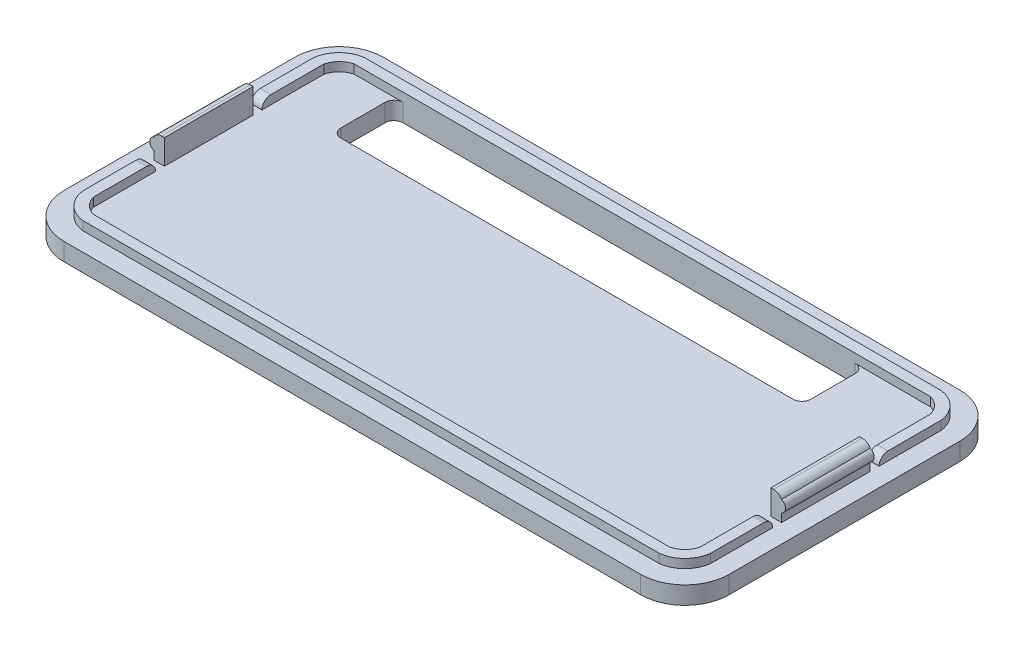
SolidWorks part; units mm, degrees
ref_plane "前视基准面" through (0, 0, 0) normal (0, 0, 1) x (1, 0, 0)
ref_plane "上视基准面" through (0, 0, 0) normal (0, 1, 0) x (1, 0, 0)
ref_plane "右视基准面" through (0, 0, 0) normal (1, 0, 0) x (0, 0, -1)
sketch "zero" plane through (0, 0, 0) normal (0, 1, 0) x (1, 0, 0)
  line L1 (-29.5, 15) -> (29.5, 15)
  line L2 (-32.5, 12) -> (-32.5, -12)
  line L3 (-29.5, -15) -> (29.5, -15)
  line L4 (32.5, 12) -> (32.5, -12)
  line L5 (-32.5, 15) -> (32.5, -15) construction
  line L6 (-32.5, -15) -> (32.5, 15) construction
  line L7 (-25.7, -15) -> (-14.5, -15)
  line L8 (-25.7, -15) -> (-25.7, -9.6569)
  line L9 (-25.7, -9.6569) -> (-14.5, -9.6569)
  line L10 (-14.5, -15) -> (-14.5, -9.6569)
  line L11 (5.2, -15) -> (12.7, -15)
  line L12 (5.2, -15) -> (5.2, -11)
  line L13 (5.2, -11) -> (12.7, -11)
  line L14 (12.7, -15) -> (12.7, -11)
  line L15 (17.8, -15) -> (25.3, -15)
  line L16 (17.8, -15) -> (17.8, -11)
  line L17 (17.8, -11) -> (25.3, -11)
  line L18 (25.3, -15) -> (25.3, -11)
  line L19 (-32.5, 7.7) -> (-19.5, 7.7)
  line L20 (-32.5, 7.7) -> (-32.5, -4.3)
  line L21 (-32.5, -4.3) -> (-19.5, -4.3)
  line L22 (-19.5, 7.7) -> (-19.5, -4.3)
  line L23 (-25.5, 14) -> (25.5, 14)
  line L24 (-25.5, 14) -> (-25.5, 8.8)
  line L25 (-25.5, 8.8) -> (25.5, 8.8)
  line L26 (25.5, 14) -> (25.5, 8.8)
  line L27 (-19.5, 7.2329) -> (-35.5, 7.2329)
  line L28 (-19.5, 7.2329) -> (-19.5, -3.7671)
  line L29 (-19.5, -3.7671) -> (-35.5, -3.7671)
  line L30 (-35.5, 7.2329) -> (-35.5, -3.7671)
  arc A0 (29.5, -15) -> (32.5, -12) centre (29.5, -12) ccw
  arc A1 (29.5, 15) -> (32.5, 12) centre (29.5, 12) cw
  arc A2 (-32.5, -12) -> (-29.5, -15) centre (-29.5, -12) ccw
  arc A3 (-29.5, 15) -> (-32.5, 12) centre (-29.5, 12) ccw
  circle A4 centre (-29, 11.4) radius 3
  circle A5 centre (-29, -11.5) radius 3
  circle A6 centre (29, 11.4) radius 3
  circle A7 centre (29, -11.5) radius 3
  circle A8 centre (-29, 11.4) radius 1.375
  circle A9 centre (-29, -11.5) radius 1.375
  circle A10 centre (29, -11.5) radius 1.375
  circle A11 centre (29, 11.4) radius 1.375
  point P0 (0, 0)
  dimension "D3" = 3
  dimension "D4" = 6
  dimension "D9" = 2.75
  dimension "D1" = 65
  dimension "D2" = 30
  dimension "D5" = 3.6
  dimension "D6" = 3.5
  dimension "D7" = 3.5
  dimension "D8" = 3.5
  dimension "D10" = 12
  dimension "D11" = 7.3
  dimension "D12" = 13
  dimension "D13" = 11.2
  dimension "D14" = 6.8
  dimension "D15" = 19.7
  dimension "D16" = 7.5
  dimension "D17" = 7.5
  dimension "D18" = 5.1
  dimension "D19" = 4
  dimension "D20" = 5.2
  dimension "D21" = 7
  dimension "D22" = 7
  dimension "D23" = 1
  dimension "D24" = 11
  dimension "D25" = 16
sketch "sugar" plane through (0, 0, 0) normal (0, 1, 0) x (1, 0, 0)
  line L1 (-29.5, 15) -> (29.5, 15)
  line L2 (-32.5, 12) -> (-32.5, -12)
  line L3 (-29.5, -15) -> (29.5, -15)
  line L4 (32.5, 12) -> (32.5, -12)
  line L5 (-32.5, 15) -> (32.5, -15) construction
  line L6 (-32.5, -15) -> (32.5, 15) construction
  line L7 (23.5, -11.5) -> (19.5, -11.5)
  line L8 (23.5, -11.5) -> (23.5, -13.9082)
  line L9 (23.5, -13.9082) -> (19.5, -13.9082)
  line L10 (19.5, -11.5) -> (19.5, -13.9082)
  line L11 (16, -11.0071) -> (8.5, -11.0071)
  line L12 (16, -11.0071) -> (16, -15)
  line L13 (16, -15) -> (8.5, -15)
  line L14 (8.5, -11.0071) -> (8.5, -15)
  line L15 (20.5, -13.9082) -> (22.5, -13.9082)
  line L16 (20.5, -13.9082) -> (20.5, -14.8173)
  line L17 (20.5, -14.8173) -> (22.5, -14.8173)
  line L18 (22.5, -13.9082) -> (22.5, -14.8173)
  arc A0 (29.5, 15) -> (32.5, 12) centre (29.5, 12) cw
  arc A1 (29.5, -15) -> (32.5, -12) centre (29.5, -12) ccw
  arc A2 (-32.5, -12) -> (-29.5, -15) centre (-29.5, -12) ccw
  arc A3 (-29.5, 15) -> (-32.5, 12) centre (-29.5, 12) ccw
  circle A4 centre (-29, 11.4) radius 3
  circle A5 centre (-29, 11.4) radius 1.375
  circle A6 centre (-29, -11.5) radius 3
  circle A7 centre (-29, -11.5) radius 1.375
  circle A8 centre (29, 11.4) radius 3
  circle A9 centre (29, 11.4) radius 1.375
  circle A10 centre (29, -11.5) radius 3
  circle A11 centre (29, -11.5) radius 1.375
  dimension "D3" = 3
  dimension "D1" = 65
  dimension "D2" = 30
  dimension "D4" = 9
  dimension "D5" = 4
  dimension "D6" = 3.5
  dimension "D7" = 7.5
  dimension "D8" = 2
  dimension "D9" = 1
sketch "case" plane through (0, 0, 0) normal (0, 1, 0) x (1, 0, 0)
  line L1 (-34.0422, 18) -> (30.9578, 18)
  line L2 (-39.0422, 13) -> (-39.0422, -13)
  line L3 (-34.0422, -18) -> (30.9578, -18)
  line L4 (35.9578, 13) -> (35.9578, -13)
  line L5 (-39.0422, 18) -> (35.9578, -18) construction
  line L6 (-39.0422, -18) -> (35.9578, 18) construction
  arc A0 (-39.0422, -13) -> (-34.0422, -18) centre (-34.0422, -13) ccw
  arc A1 (30.9578, -18) -> (35.9578, -13) centre (30.9578, -13) ccw
  arc A2 (30.9578, 18) -> (35.9578, 13) centre (30.9578, 13) cw
  arc A3 (-34.0422, 18) -> (-39.0422, 13) centre (-34.0422, 13) ccw
  point P0 (-1.5422, 0)
  point P3 (-1.5422, 0)
  dimension "D3" = 5
  dimension "D1" = 75
  dimension "D2" = 36
extrude "凸台-拉伸2" add sketch "case" along normal blind 2
sketch "草图2" plane through (0, 0, 0) normal (0, 1, 0) x (1, 0, 0)
  line L4 (-34.0422, -14.7) -> (30.9578, -14.7)
  line L5 (32.6578, -13) -> (32.6578, 13)
  line L6 (30.9578, 14.7) -> (-34.0422, 14.7)
  line L7 (-35.7422, 13) -> (-35.7422, -13)
  line L12 (33.8578, -13) -> (33.8578, 13)
  line L13 (30.9578, 15.9) -> (-34.0422, 15.9)
  line L14 (-36.9422, 13) -> (-36.9422, -13)
  line L15 (-34.0422, -15.9) -> (30.9578, -15.9)
  arc A4 (30.9578, -14.7) -> (32.6578, -13) centre (30.339, -12.3812) ccw
  arc A5 (32.6578, 13) -> (30.9578, 14.7) centre (30.339, 12.3812) ccw
  arc A6 (-34.0422, 14.7) -> (-35.7422, 13) centre (-33.4234, 12.3812) ccw
  arc A7 (-35.7422, -13) -> (-34.0422, -14.7) centre (-33.4234, -12.3812) ccw
  arc A12 (30.9578, -15.9) -> (33.8578, -13) centre (30.5796, -12.6217) ccw
  arc A13 (33.8578, 13) -> (30.9578, 15.9) centre (30.5796, 12.6217) ccw
  arc A14 (-34.0422, 15.9) -> (-36.9422, 13) centre (-33.6639, 12.6217) ccw
  arc A15 (-36.9422, -13) -> (-34.0422, -15.9) centre (-33.6639, -12.6217) ccw
ref_plane "基准面1" through (0, 2, 0) normal (0, 1, 0) x (1, 0, 0)
sketch "草图3" plane through (0, 2, 0) normal (0, 1, 0) x (1, 0, 0)
  line L4 (-34.0422, -14.7) -> (30.9578, -14.7)
  line L5 (32.6578, -13) -> (32.6578, 13)
  line L6 (30.9578, 14.7) -> (-34.0422, 14.7)
  line L7 (-35.7422, 13) -> (-35.7422, -13)
  line L8 (-34.0422, -14.7) -> (30.9578, -14.7)
  line L9 (32.6578, -13) -> (32.6578, 13)
  line L10 (30.9578, 14.7) -> (-34.0422, 14.7)
  line L11 (-35.7422, 13) -> (-35.7422, -13)
  line L12 (-36.9422, 13) -> (-36.9422, -13)
  line L13 (-34.0422, -15.9) -> (30.9578, -15.9)
  line L14 (33.8578, -13) -> (33.8578, 13)
  line L15 (30.9578, 15.9) -> (-34.0422, 15.9)
  line L16 (-36.9422, 13) -> (-36.9422, -13)
  line L17 (-34.0422, -15.9) -> (30.9578, -15.9)
  line L18 (33.8578, -13) -> (33.8578, 13)
  line L19 (30.9578, 15.9) -> (-34.0422, 15.9)
  arc A4 (30.9578, -14.7) -> (32.6578, -13) centre (30.339, -12.3812) ccw
  arc A5 (32.6578, 13) -> (30.9578, 14.7) centre (30.339, 12.3812) ccw
  arc A6 (-34.0422, 14.7) -> (-35.7422, 13) centre (-33.4234, 12.3812) ccw
  arc A7 (-35.7422, -13) -> (-34.0422, -14.7) centre (-33.4234, -12.3812) ccw
  arc A8 (30.9578, -14.7) -> (32.6578, -13) centre (30.339, -12.3812) ccw
  arc A9 (32.6578, 13) -> (30.9578, 14.7) centre (30.339, 12.3812) ccw
  arc A10 (-34.0422, 14.7) -> (-35.7422, 13) centre (-33.4234, 12.3812) ccw
  arc A11 (-35.7422, -13) -> (-34.0422, -14.7) centre (-33.4234, -12.3812) ccw
  arc A12 (-36.9422, -13) -> (-34.0422, -15.9) centre (-33.6639, -12.6217) ccw
  arc A13 (30.9578, -15.9) -> (33.8578, -13) centre (30.5796, -12.6217) ccw
  arc A14 (33.8578, 13) -> (30.9578, 15.9) centre (30.5796, 12.6217) ccw
  arc A15 (-34.0422, 15.9) -> (-36.9422, 13) centre (-33.6639, 12.6217) ccw
  arc A16 (-36.9422, -13) -> (-34.0422, -15.9) centre (-33.6639, -12.6217) ccw
  arc A17 (30.9578, -15.9) -> (33.8578, -13) centre (30.5796, -12.6217) ccw
  arc A18 (33.8578, 13) -> (30.9578, 15.9) centre (30.5796, 12.6217) ccw
  arc A19 (-34.0422, 15.9) -> (-36.9422, 13) centre (-33.6639, 12.6217) ccw
  dimension "D1" = 0
  dimension "D2" = 0
extrude "凸台-拉伸4" add sketch "草图3" along normal blind 1
ref_plane "基准面3" through (33.8578, 0, 0) normal (1, 0, 0) x (0, 0, -1)
sketch "草图7" plane through (0, 2, 0) normal (0, 1, 0) x (1, 0, 0)
  line L0 (-36.9422, 13) -> (-36.9422, -13) construction
  line L1 (-36.9422, 5) -> (-35.7422, 5)
  line L2 (-36.9422, 5) -> (-36.9422, -5)
  line L3 (-36.9422, -5) -> (-35.7422, -5)
  line L4 (-35.7422, 5) -> (-35.7422, -5)
  line L5 (-35.7422, 13) -> (-35.7422, -13) construction
  point P10 (-35.7422, 0)
  dimension "D1" = 5
  dimension "D2" = 10
extrude "凸台-拉伸8" add sketch "草图7" along normal blind 2.8
ref_plane "基准面5" through (0, 0, 5) normal (0, 0, 1) x (1, 0, 0)
sketch "草图8" plane through (0, 0, 5) normal (0, 0, 1) x (1, 0, 0)
  line L0 (-34.0422, 2) -> (-39.0422, 2) construction
  line L1 (-36.9422, 4.8) -> (-36.9422, 3) construction
  circle A0 centre (-36.6922, 3.6) radius 0.7
  dimension "D1" = 1.4
  dimension "D2" = 1.6
  dimension "D3" = 0.25
extrude "凸台-拉伸9" add sketch "草图8" against normal blind 10
fillet "圆角1" radius 1 1 edges at (-36.9422, 4.8, 0)
ref_plane "基准面7" through (-36.9422, 0, 0) normal (-1, 0, 0) x (0, 0, 1)
sketch "草图11" plane through (-36.9422, 0, 0) normal (-1, 0, 0) x (0, 0, 1)
  line L0 (-13, 2) -> (13, 2) construction
  line L1 (5, 3) -> (6, 3)
  line L2 (5, 3) -> (5, 2)
  line L3 (5, 2) -> (6, 2)
  line L4 (6, 3) -> (6, 2)
  line L6 (-5, 3) -> (-6, 3)
  line L7 (-5, 3) -> (-5, 2)
  line L8 (-5, 2) -> (-6, 2)
  line L9 (-6, 3) -> (-6, 2)
  dimension "D1" = 1
  dimension "D2" = 1
extrude "切除-拉伸1" cut sketch "草图11" against normal blind 1.2
fillet "圆角2" radius 1 2 edges at (-36.3422, 3, 6) (-36.3422, 3, -6)
ref_plane "基准面8" through (0, 0, 0) normal (0, -1, 0) x (-1, 0, 0)
sketch "草图12" plane through (0, 0, 0) normal (0, -1, 0) x (-1, 0, 0)
  line L76 (34.0422, -18) -> (-30.9578, -18) construction
  line L78 (39.0422, 13) -> (39.0422, -13) construction
  line B0 (-8.1993, 1.426) -> (-9.0198, 1.899)
  line B1 (-9.0198, 1.899) -> (-13.2767, 4.3551)
  line B2 (-13.2767, 4.3551) -> (-14.0973, 4.8339)
  line B3 (-15.8183, 4.8339) -> (-16.6389, 4.3551)
  line B4 (-16.6389, 4.3551) -> (-20.8958, 1.899)
  line B5 (-20.8958, 1.899) -> (-21.7165, 1.426)
  line B6 (-22.577, -0.0613) -> (-22.577, -6.8769)
  line B7 (-21.7165, -8.3643) -> (-20.8958, -8.8373)
  line B8 (-20.8958, -8.8373) -> (-16.6389, -11.2934)
  line B9 (-16.6389, -11.2934) -> (-15.8183, -11.772)
  line B10 (-14.0973, -11.772) -> (-13.2767, -11.2934)
  line B11 (-13.2767, -11.2934) -> (-9.0198, -8.8373)
  line B12 (-9.0198, -8.8373) -> (-8.1993, -8.3643)
  line B13 (-7.3388, -6.8769) -> (-7.3388, -0.0613)
  line B14 (-20.6223, 0.7479) -> (-15.3568, 3.791)
  line B15 (-14.5532, 3.791) -> (-9.3162, 0.7422)
  line B16 (-9.3105, 0.0413) -> (-14.3993, -3.0018)
  line B17 (-12.8208, -8.1591) -> (-13.4135, -8.4896)
  line B18 (-13.4705, -8.5865) -> (-13.4705, -10.2961)
  line B19 (-13.5274, -10.393) -> (-14.633, -11.0198)
  line B20 (-14.7983, -10.9229) -> (-14.7983, -5.646)
  line B21 (-14.7413, -5.5491) -> (-12.8607, -4.4835)
  line B22 (-8.9173, -7.8058) -> (-10.0114, -8.4269)
  line B23 (-10.1767, -8.3301) -> (-10.1767, -5.8169)
  line B24 (-10.1197, -5.7201) -> (-9.0256, -5.1046)
  line B25 (-8.8603, -5.2015) -> (-8.8603, -7.7089)
  line B26 (-12.8893, -7.1447) -> (-13.4135, -7.4069)
  line B27 (-13.4705, -7.2872) -> (-13.4705, -5.9423)
  line B28 (-13.4135, -5.8455) -> (-12.9234, -5.5719)
  line B29 (-3.344, -0.54) -> (-5.2189, -0.54)
  line B30 (-5.2189, -0.54) -> (-5.2189, -7.1048)
  line B31 (-5.2189, -7.1048) -> (-4.3868, -7.1048)
  line B32 (-4.3868, -7.1048) -> (-4.3868, -4.5005)
  line B33 (-4.3868, -4.5005) -> (-3.2984, -4.5005)
  line B34 (-3.4066, -3.8281) -> (-4.3868, -3.8281)
  line B35 (-4.3868, -3.8281) -> (-4.3868, -1.2124)
  line B36 (-4.3868, -1.2124) -> (-3.4408, -1.2124)
  line B37 (0.1948, -2.2382) -> (0.1948, -7.1048)
  line B38 (0.1948, -7.1048) -> (1.0098, -7.1048)
  line B39 (1.0098, -7.1048) -> (1.0098, -2.2382)
  line B40 (1.0098, -2.2382) -> (0.1948, -2.2382)
  line B41 (5.7169, -3.3153) -> (4.8849, -2.9847)
  line B42 (6.0417, -2.1983) -> (6.8396, -1.1953)
  line B43 (3.6084, -4.1586) -> (4.4575, -4.5177)
  line B44 (2.9074, -5.1673) -> (2.0014, -6.2729)
  line B45 (10.8229, -2.0102) -> (10.8229, -5.3497)
  line B46 (9.3811, -4.9621) -> (9.3811, -2.0102)
  line B47 (9.3811, -2.0102) -> (7.7912, -2.0102)
  line B48 (7.7912, -2.0102) -> (7.7912, -5.1616)
  line B49 (10.9711, -6.4039) -> (11.0052, -6.4039)
  line B50 (11.0052, -6.4039) -> (11.1193, -7.1048)
  line B51 (11.1193, -7.1048) -> (12.4185, -7.1048)
  line B52 (12.4185, -7.1048) -> (12.4185, -2.0102)
  line B53 (12.4185, -2.0102) -> (10.8229, -2.0102)
  line B54 (16.2708, -6.1019) -> (15.4673, -6.1019)
  line B55 (17.365, -3.1614) -> (18.1513, -3.1614)
  line B56 (18.1513, -3.1614) -> (18.1513, -2.0102)
  line B57 (18.1513, -2.0102) -> (16.2822, -2.0102)
  line B58 (14.0312, -5.0533) -> (14.0312, -5.0875)
  line B59 (13.9344, -6.9168) -> (13.9344, -6.9624)
  line B60 (15.4844, -7.3214) -> (15.9688, -7.3214)
  line B61 (18.6072, -2.5516) -> (19.1657, -3.6002)
  line B62 (21.411, -6.592) -> (21.4508, -6.592)
  line B63 (21.4508, -6.592) -> (21.5648, -7.1048)
  line B64 (21.5648, -7.1048) -> (22.8641, -7.1048)
  line B65 (22.8641, -7.1048) -> (22.8641, -4.2099)
  line B66 (21.2685, -4.7741) -> (21.2685, -5.589)
  line B67 (25.3545, -2.8935) -> (25.3203, -2.8935)
  line B68 (25.3203, -2.8935) -> (25.212, -2.0102)
  line B69 (25.212, -2.0102) -> (23.9127, -2.0102)
  line B70 (23.9127, -2.0102) -> (23.9127, -7.1048)
  line B71 (23.9127, -7.1048) -> (25.4969, -7.1048)
  line B72 (25.4969, -7.1048) -> (25.4969, -4.1928)
  line B73 (27.1552, -3.3608) -> (27.423, -1.9875)
  line B74 (-13.4135, -7.4069) -> (-13.4135, -8.4896)
  line B75 (-13.4705, -7.2872) -> (-13.4705, -8.5865)
  spline B76 degree 3 poles (-14.0973, 4.8339) (-14.3652, 4.982) (-14.6615, 5.0618) (-14.9578, 5.0618) knots 3 3 3 3 4 4 4 4
  spline B77 degree 3 poles (-14.9578, 5.0618) (-15.2541, 5.0618) (-15.5505, 4.982) (-15.8183, 4.8339) knots 4 4 4 4 5 5 5 5
  spline B78 degree 3 poles (-21.7165, 1.426) (-22.2464, 1.1183) (-22.577, 0.5485) (-22.577, -0.0613) knots 8 8 8 8 9 9 9 9
  spline B79 degree 3 poles (-22.577, -6.8769) (-22.577, -7.4923) (-22.2464, -8.0565) (-21.7165, -8.3643) knots 10 10 10 10 11 11 11 11
  spline B80 degree 3 poles (-15.8183, -11.772) (-15.5505, -11.9259) (-15.2541, -12) (-14.9578, -12) knots 14 14 14 14 15 15 15 15
  spline B81 degree 3 poles (-14.9578, -12) (-14.6615, -12) (-14.3652, -11.9259) (-14.0973, -11.772) knots 15 15 15 15 16 16 16 16
  spline B82 degree 3 poles (-8.1993, -8.3643) (-7.6636, -8.0565) (-7.3388, -7.4923) (-7.3388, -6.8769) knots 19 19 19 19 20 20 20 20
  spline B83 degree 3 poles (-7.3388, -0.0613) (-7.3388, 0.5485) (-7.6636, 1.1183) (-8.1993, 1.426) knots 21 21 21 21 22 22 22 22
  spline B84 degree 2 poles (-15.5106, -3.0018) (-20.6622, -0.0271) (-20.6736, -0.0214) knots 0 0 0 1 1 1
  spline B85 degree 3 poles (-20.6736, -0.0214) (-20.9414, 0.1723) (-20.9129, 0.5826) (-20.6223, 0.7479) knots 1 1 1 1 2 2 2 2
  spline B86 degree 3 poles (-15.3568, 3.791) (-15.1117, 3.9335) (-14.8039, 3.9335) (-14.5532, 3.791) knots 3 3 3 3 4 4 4 4
  spline B87 degree 3 poles (-9.3162, 0.7422) (-9.0484, 0.5883) (-9.0427, 0.2008) (-9.3105, 0.0413) knots 5 5 5 5 6 6 6 6
  spline B88 degree 3 poles (-14.3993, -3.0018) (-14.7413, -3.2013) (-15.1687, -3.2013) (-15.5106, -3.0018) knots 7 7 7 7 8 8 8 8
  spline B89 degree 3 poles (-13.4705, -10.2961) (-13.4705, -10.336) (-13.4876, -10.3702) (-13.5274, -10.393) knots 3 3 3 3 4 4 4 4
  spline B90 degree 3 poles (-14.633, -11.0198) (-14.7071, -11.0597) (-14.7983, -11.0084) (-14.7983, -10.9229) knots 5 5 5 5 6 6 6 6
  spline B91 degree 3 poles (-14.7983, -5.646) (-14.7983, -5.6061) (-14.7812, -5.5662) (-14.7413, -5.5491) knots 7 7 7 7 8 8 8 8
  spline B92 degree 3 poles (-12.8607, -4.4835) (-11.6412, -3.7939) (-10.6326, -3.6572) (-10.6326, -5.0249) knots 9 9 9 9 10 10 10 10
  spline B93 degree 3 poles (-10.6326, -5.0249) (-10.6326, -6.3412) (-11.6526, -7.498) (-12.8208, -8.1591) knots 10 10 10 10 11 11 11 11
  spline B94 degree 3 poles (-8.8603, -7.7089) (-8.8603, -7.7488) (-8.8831, -7.7887) (-8.9173, -7.8058) knots 0 0 0 0 1 1 1 1
  spline B95 degree 3 poles (-10.0114, -8.4269) (-10.0855, -8.4668) (-10.1767, -8.4155) (-10.1767, -8.3301) knots 2 2 2 2 3 3 3 3
  spline B96 degree 3 poles (-10.1767, -5.8169) (-10.1767, -5.7771) (-10.1539, -5.7429) (-10.1197, -5.7201) knots 4 4 4 4 5 5 5 5
  spline B97 degree 3 poles (-9.0256, -5.1046) (-8.9515, -5.0647) (-8.8603, -5.116) (-8.8603, -5.2015) knots 6 6 6 6 7 7 7 7
  spline B98 degree 3 poles (-9.5156, -3.4349) (-9.0768, -3.1842) (-8.7634, -3.2924) (-8.7634, -3.6914) (-8.7634, -4.0846) (-9.0768, -4.5461) (-9.5156, -4.7912) knots 2 2 2 2 3 3 3 4 4 4 4
  spline B99 degree 3 poles (-9.5156, -4.7912) (-9.9601, -5.0476) (-10.2735, -4.9394) (-10.2735, -4.5461) (-10.2735, -4.1415) (-9.9601, -3.6856) (-9.5156, -3.4349) knots 0 0 0 0 1 1 1 2 2 2 2
  spline B100 degree 3 poles (-11.9319, -5.76) (-11.9319, -6.3013) (-12.2395, -6.78) (-12.8893, -7.1447) knots 0 0 0 0 1 1 1 1
  spline B101 degree 3 poles (-13.4705, -5.9423) (-13.4705, -5.9024) (-13.4477, -5.8625) (-13.4135, -5.8455) knots 4 4 4 4 5 5 5 5
  spline B102 degree 3 poles (-12.9234, -5.5719) (-12.2852, -5.2072) (-11.9319, -5.2015) (-11.9319, -5.76) knots 6 6 6 6 7 7 7 7
  spline B103 degree 3 poles (-3.2984, -4.5005) (-1.868, -4.5005) (-0.8822, -3.8509) (-0.8822, -2.4661) knots 5 5 5 5 6 6 6 6
  spline B104 degree 3 poles (-0.8822, -2.4661) (-0.8822, -1.0301) (-1.868, -0.54) (-3.344, -0.54) knots 6 6 6 6 7 7 7 7
  spline B105 degree 3 poles (-3.4408, -1.2124) (-2.2897, -1.2124) (-1.7084, -1.5145) (-1.7084, -2.4661) knots 3 3 3 3 4 4 4 4
  spline B106 degree 3 poles (-1.7084, -2.4661) (-1.7084, -3.4064) (-2.2498, -3.8281) (-3.4066, -3.8281) knots 4 4 4 4 5 5 5 5
  spline B107 degree 3 poles (0.6052, -1.2352) (0.93, -1.2352) (1.1694, -1.013) (1.1694, -0.711) (1.1694, -0.3747) (0.93, -0.181) (0.6052, -0.181) knots 2 2 2 2 3 3 3 4 4 4 4
  spline B108 degree 3 poles (0.6052, -0.181) (0.2804, -0.181) (0.041, -0.3747) (0.041, -0.711) (0.041, -1.013) (0.2804, -1.2352) (0.6052, -1.2352) knots 0 0 0 0 1 1 1 2 2 2 2
  spline B109 degree 3 poles (4.8849, -2.9847) (4.2979, -2.7511) (3.8762, -2.6086) (3.8762, -2.2382) knots 1 1 1 1 2 2 2 2
  spline B110 degree 3 poles (3.8762, -2.2382) (3.8762, -1.8849) (4.1783, -1.6854) (4.674, -1.6854) knots 2 2 2 2 3 3 3 3
  spline B111 degree 3 poles (4.674, -1.6854) (5.1926, -1.6854) (5.6029, -1.8621) (6.0417, -2.1983) knots 3 3 3 3 4 4 4 4
  spline B112 degree 3 poles (6.8396, -1.1953) (6.2583, -0.6084) (5.4433, -0.3121) (4.674, -0.3121) knots 5 5 5 5 6 6 6 6
  spline B113 degree 3 poles (4.674, -0.3121) (3.2551, -0.3121) (2.2521, -1.2124) (2.2521, -2.3294) knots 6 6 6 6 7 7 7 7
  spline B114 degree 3 poles (2.2521, -2.3294) (2.2521, -3.2981) (2.9074, -3.8794) (3.6084, -4.1586) knots 7 7 7 7 8 8 8 8
  spline B115 degree 3 poles (4.4575, -4.5177) (5.0274, -4.757) (5.3978, -4.8824) (5.3978, -5.2699) knots 9 9 9 9 10 10 10 10
  spline B116 degree 3 poles (5.3978, -5.2699) (5.3978, -5.6289) (5.1185, -5.8511) (4.5259, -5.8511) knots 10 10 10 10 11 11 11 11
  spline B117 degree 3 poles (4.5259, -5.8511) (4.0016, -5.8511) (3.3804, -5.5719) (2.9074, -5.1673) knots 11 11 11 11 12 12 12 12
  spline B118 degree 3 poles (2.0014, -6.2729) (2.6909, -6.9054) (3.6254, -7.2302) (4.4916, -7.2302) knots 13 13 13 13 14 14 14 14
  spline B119 degree 3 poles (4.4916, -7.2302) (6.1044, -7.2302) (7.0389, -6.2557) (7.0389, -5.1445) knots 14 14 14 14 15 15 15 15
  spline B120 degree 3 poles (7.0389, -5.1445) (7.0389, -4.2042) (6.5432, -3.6458) (5.7169, -3.3153) knots 15 15 15 15 16 16 16 16
  spline B121 degree 3 poles (10.8229, -5.3497) (10.5551, -5.7258) (10.3328, -5.8682) (9.9738, -5.8682) knots 1 1 1 1 2 2 2 2
  spline B122 degree 3 poles (9.9738, -5.8682) (9.5692, -5.8682) (9.3811, -5.6688) (9.3811, -4.9621) knots 2 2 2 2 3 3 3 3
  spline B123 degree 3 poles (7.7912, -5.1616) (7.7912, -6.4324) (8.2642, -7.2302) (9.3754, -7.2302) knots 6 6 6 6 7 7 7 7
  spline B124 degree 3 poles (9.3754, -7.2302) (10.0706, -7.2302) (10.5494, -6.9054) (10.9711, -6.4039) knots 7 7 7 7 8 8 8 8
  spline B125 degree 3 poles (15.4673, -6.1019) (14.9202, -6.1019) (14.7151, -5.9936) (14.7151, -5.76) knots 1 1 1 1 2 2 2 2
  spline B126 degree 3 poles (14.7151, -5.76) (14.7151, -5.589) (14.7549, -5.5092) (14.8746, -5.4009) knots 2 2 2 2 3 3 3 3
  spline B127 degree 3 poles (14.8746, -5.4009) (15.0969, -5.4636) (15.302, -5.4921) (15.473, -5.4921) knots 3 3 3 3 4 4 4 4
  spline B128 degree 3 poles (15.473, -5.4921) (16.6013, -5.4921) (17.5074, -4.9735) (17.5074, -3.7825) knots 4 4 4 4 5 5 5 5
  spline B129 degree 3 poles (17.5074, -3.7825) (17.5074, -3.5375) (17.4447, -3.3038) (17.365, -3.1614) knots 5 5 5 5 6 6 6 6
  spline B130 degree 3 poles (16.2822, -2.0102) (16.0485, -1.9248) (15.7693, -1.8849) (15.473, -1.8849) knots 9 9 9 9 10 10 10 10
  spline B131 degree 3 poles (15.473, -1.8849) (14.3732, -1.8849) (13.3417, -2.4889) (13.3417, -3.7369) knots 10 10 10 10 11 11 11 11
  spline B132 degree 3 poles (13.3417, -3.7369) (13.3417, -4.3296) (13.6722, -4.8026) (14.0312, -5.0533) knots 11 11 11 11 12 12 12 12
  spline B133 degree 3 poles (14.0312, -5.0875) (13.7007, -5.3212) (13.467, -5.6802) (13.467, -6.0392) knots 13 13 13 13 14 14 14 14
  spline B134 degree 3 poles (13.467, -6.0392) (13.467, -6.4666) (13.6665, -6.7344) (13.9344, -6.9168) knots 14 14 14 14 15 15 15 15
  spline B135 degree 3 poles (13.9344, -6.9624) (13.4613, -7.2017) (13.2106, -7.5436) (13.2106, -7.9653) knots 16 16 16 16 17 17 17 17
  spline B136 degree 3 poles (13.2106, -7.9653) (13.2106, -8.8771) (14.1737, -9.2475) (15.3476, -9.2475) knots 17 17 17 17 18 18 18 18
  spline B137 degree 3 poles (15.3476, -9.2475) (17.1199, -9.2475) (18.2312, -8.4839) (18.2312, -7.4069) knots 18 18 18 18 19 19 19 19
  spline B138 degree 3 poles (18.2312, -7.4069) (18.2312, -6.4837) (17.5245, -6.1019) (16.2708, -6.1019) knots 19 19 19 19 20 20 20 20
  spline B139 degree 3 poles (15.473, -4.5347) (15.1083, -4.5347) (14.8291, -4.2669) (14.8291, -3.7369) (14.8291, -3.2184) (15.1083, -2.9505) (15.473, -2.9505) knots 2 2 2 2 3 3 3 4 4 4 4
  spline B140 degree 3 poles (15.473, -2.9505) (15.8491, -2.9505) (16.1169, -3.2184) (16.1169, -3.7369) (16.1169, -4.2669) (15.8491, -4.5347) (15.473, -4.5347) knots 0 0 0 0 1 1 1 2 2 2 2
  spline B141 degree 3 poles (15.5983, -8.2503) (14.943, -8.2503) (14.5156, -8.0736) (14.5156, -7.7146) knots 0 0 0 0 1 1 1 1
  spline B142 degree 3 poles (14.5156, -7.7146) (14.5156, -7.5436) (14.5953, -7.4012) (14.7549, -7.2587) knots 1 1 1 1 2 2 2 2
  spline B143 degree 3 poles (14.7549, -7.2587) (14.9202, -7.3043) (15.114, -7.3214) (15.4844, -7.3214) knots 2 2 2 2 3 3 3 3
  spline B144 degree 3 poles (15.9688, -7.3214) (16.4417, -7.3214) (16.7096, -7.3841) (16.7096, -7.6861) knots 4 4 4 4 5 5 5 5
  spline B145 degree 3 poles (16.7096, -7.6861) (16.7096, -8.0109) (16.2537, -8.2503) (15.5983, -8.2503) knots 5 5 5 5 6 6 6 6
  spline B146 degree 3 poles (20.8013, -1.8849) (20.0091, -1.8849) (19.2797, -2.1527) (18.6072, -2.5516) knots 0 0 0 0 1 1 1 1
  spline B147 degree 3 poles (19.1657, -3.6002) (19.6729, -3.3153) (20.0946, -3.1557) (20.4992, -3.1557) knots 2 2 2 2 3 3 3 3
  spline B148 degree 3 poles (20.4992, -3.1557) (21.0177, -3.1557) (21.2344, -3.395) (21.2685, -3.8053) knots 3 3 3 3 4 4 4 4
  spline B149 degree 3 poles (21.2685, -3.8053) (19.2797, -4.0219) (18.4362, -4.6031) (18.4362, -5.6802) knots 4 4 4 4 5 5 5 5
  spline B150 degree 3 poles (18.4362, -5.6802) (18.4362, -6.5293) (19.0118, -7.2302) (19.9522, -7.2302) knots 5 5 5 5 6 6 6 6
  spline B151 degree 3 poles (19.9522, -7.2302) (20.5163, -7.2302) (20.9893, -6.9681) (21.411, -6.592) knots 6 6 6 6 7 7 7 7
  spline B152 degree 3 poles (22.8641, -4.2099) (22.8641, -2.6143) (22.1176, -1.8849) (20.8013, -1.8849) knots 11 11 11 11 12 12 12 12
  spline B153 degree 3 poles (21.2685, -5.589) (21.0349, -5.8398) (20.824, -5.9936) (20.4992, -5.9936) knots 0 0 0 0 1 1 1 1
  spline B154 degree 3 poles (20.4992, -5.9936) (20.1686, -5.9936) (19.9522, -5.8511) (19.9522, -5.5548) knots 1 1 1 1 2 2 2 2
  spline B155 degree 3 poles (19.9522, -5.5548) (19.9522, -5.1958) (20.277, -4.9109) (21.2685, -4.7741) knots 2 2 2 2 3 3 3 3
  spline B156 degree 3 poles (26.8076, -1.8849) (26.2947, -1.8849) (25.7305, -2.2154) (25.3545, -2.8935) knots 0 0 0 0 1 1 1 1
  spline B157 degree 3 poles (25.4969, -4.1928) (25.7648, -3.5204) (26.2207, -3.2811) (26.5967, -3.2811) knots 7 7 7 7 8 8 8 8
  spline B158 degree 3 poles (26.5967, -3.2811) (26.8247, -3.2811) (26.9729, -3.3153) (27.1552, -3.3608) knots 8 8 8 8 9 9 9 9
  spline B159 degree 3 poles (27.423, -1.9875) (27.2806, -1.9248) (27.1096, -1.8849) (26.8076, -1.8849) knots 10 10 10 10 11 11 11 11
  dimension "D1" = 6
  dimension "D2" = 54
sketch_block_instance "块1-1"
sketch_block "块1"
extrude "切除-拉伸2" cut sketch "草图12" against normal blind 0.5
sketch "草图13" plane through (0, 0, 0) normal (0, 1, 0) x (1, 0, 0)
  line L0 (30.9578, 18) -> (-34.0422, 18) construction
  line L1 (-29.5422, 14.7) -> (23.4578, 14.7)
  line L2 (-29.5422, 14.7) -> (-29.5422, 7.7)
  line L3 (-29.5422, 7.7) -> (23.4578, 7.7)
  line L4 (23.4578, 14.7) -> (23.4578, 7.7)
  line L6 (-39.0422, 13) -> (-39.0422, -13) construction
  dimension "D1" = 7
  dimension "D2" = 53
  dimension "D3" = 3.3
  dimension "D4" = 9.5
extrude "切除-拉伸3" cut sketch "草图13" along normal blind 2
fillet "圆角3" radius 1 4 edges at (-29.5422, 1, -14.7) (-29.5422, 1, -7.7) (23.4578, 1, -14.7) (23.4578, 1, -7.7)
sketch "草图14" plane through (0, 3, 0) normal (0, 1, 0) x (1, 0, 0)
  line L0 (33.8578, -13) -> (33.8578, 13) construction
  line L1 (33.8578, 5) -> (32.6578, 5)
  line L2 (33.8578, 5) -> (33.8578, -5)
  line L3 (33.8578, -5) -> (32.6578, -5)
  line L4 (32.6578, 5) -> (32.6578, -5)
  line L5 (32.6578, -13) -> (32.6578, 13) construction
  line L6 (35.9578, -13) -> (35.9578, 13) construction
  point P10 (33.8578, 0)
  point P11 (35.9578, 0)
  dimension "D1" = 10
extrude "凸台-拉伸10" add sketch "草图14" along normal blind 1.8
sketch "草图15" plane through (0, 0, -5) normal (0, 0, -1) x (-1, 0, 0)
  line L0 (-30.9578, 2) -> (-35.9578, 2) construction
  line L1 (-33.8578, 4.8) -> (-33.8578, 3) construction
  circle A0 centre (-33.6078, 3.6) radius 0.7
  dimension "D1" = 1.4
  dimension "D2" = 1.6
  dimension "D3" = 0.25
extrude "凸台-拉伸11" add sketch "草图15" against normal blind 10 contours A0
fillet "圆角4" radius 1 1 edges at (33.8578, 4.8, 0)
sketch "草图16" plane through (0, 3, 0) normal (0, 1, 0) x (1, 0, 0)
  line L0 (33.8578, -13) -> (33.8578, -5) construction
  line L1 (32.6578, -5) -> (33.8578, -5)
  line L2 (32.6578, -5) -> (32.6578, -6)
  line L3 (32.6578, -6) -> (33.8578, -6)
  line L4 (33.8578, -5) -> (33.8578, -6)
  line L5 (33.8578, 5) -> (33.8578, 13) construction
  line L6 (32.6578, 5) -> (33.8578, 5)
  line L7 (32.6578, 5) -> (32.6578, 6)
  line L8 (32.6578, 6) -> (33.8578, 6)
  line L9 (33.8578, 5) -> (33.8578, 6)
  dimension "D1" = 1
  dimension "D2" = 1
extrude "切除-拉伸4" cut sketch "草图16" against normal blind 1
fillet "圆角5" radius 1 2 edges at (33.2578, 3, 6) (33.2578, 3, -6)
